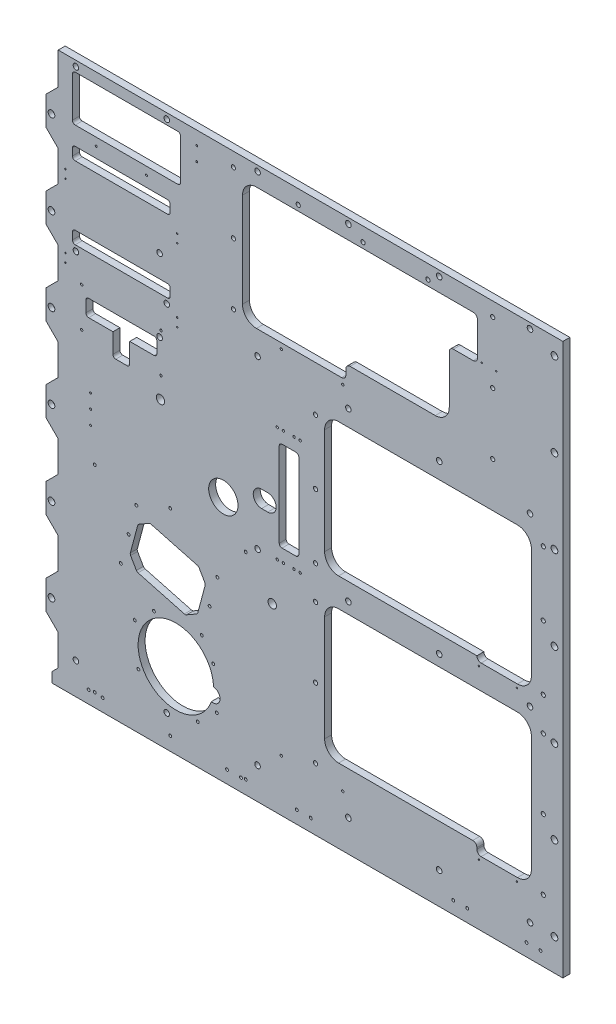
SolidWorks part; units mm, degrees
ref_plane "前视基准面" through (0, 0, 0) normal (0, 0, 1) x (1, 0, 0)
ref_plane "上视基准面" through (0, 0, 0) normal (0, 1, 0) x (1, 0, 0)
ref_plane "右视基准面" through (0, 0, 0) normal (1, 0, 0) x (0, 0, -1)
sketch "草图1" plane through (0, 0, 0) normal (0, 0, 1) x (1, 0, 0)
  line L1 (-930, 986.5) -> (930, 986.5)
  line L2 (-930, 986.5) -> (-930, -986.5)
  line L3 (-930, -986.5) -> (930, -986.5)
  line L4 (930, 986.5) -> (930, -986.5)
  line L5 (-930, 986.5) -> (930, -986.5) construction
  line L6 (-930, -986.5) -> (930, 986.5) construction
  point P0 (0, 0)
  dimension "D1" = 1973
  dimension "D2" = 1860
base flange "基体-法兰1" sketch "草图1" thickness 25 reverse thickness direction no parameters "D1"=1
sketch "草图6" plane through (0, 0, 0) normal (0, 0, 1) x (1, 0, 0)
  line L0 (-876, 871.5) -> (-919, 828.5)
  line L1 (-876, 986.5) -> (-930, 986.5)
  line L2 (-919, 828.5) -> (-919, 724.5)
  line L3 (-919, 724.5) -> (-876, 681.5)
  line L4 (-876, 571.5) -> (-919, 528.5)
  line L5 (-919, 528.5) -> (-919, 424.5)
  line L6 (-919, 424.5) -> (-876, 381.5)
  line L7 (-876, 271.5) -> (-919, 228.5)
  line L8 (-919, 228.5) -> (-919, 124.5)
  line L9 (-919, 124.5) -> (-876, 81.5)
  line L10 (-876, -28.5) -> (-919, -71.5)
  line L11 (-919, -71.5) -> (-919, -175.5)
  line L12 (-919, -175.5) -> (-876, -218.5)
  line L13 (-876, -328.5) -> (-919, -371.5)
  line L14 (-919, -371.5) -> (-919, -475.5)
  line L15 (-919, -475.5) -> (-876, -518.5)
  line L16 (-876, -628.5) -> (-919, -671.5)
  line L17 (-919, -671.5) -> (-919, -775.5)
  line L18 (-919, -775.5) -> (-876, -818.5)
  line L19 (930, 986.5) -> (-930, 986.5) construction
  line L20 (-876, -928.5) -> (-897.5, -950)
  line L21 (-897.5, -950) -> (-897.5, -986.5)
  line L22 (-930, -986.5) -> (930, -986.5) construction
  line L23 (-876, -818.5) -> (-876, -928.5)
  line L24 (-930, 986.5) -> (-930, -986.5)
  line L25 (-876, 871.5) -> (-876, 986.5)
  line L26 (-876, 681.5) -> (-876, 571.5)
  line L27 (-876, 381.5) -> (-876, 271.5)
  line L28 (-876, 81.5) -> (-876, -28.5)
  line L29 (-876, -218.5) -> (-876, -328.5)
  line L30 (-876, -518.5) -> (-876, -628.5)
  line L31 (-930, 986.5) -> (-930, -986.5) construction
  line L32 (-930, -986.5) -> (-897.5, -986.5)
  point P30 (-897.5, -968.25)
  dimension "D1" = 115
  dimension "D3" = 43
  dimension "D4" = 104
  dimension "D5" = 110
  dimension "D6" = 190
  dimension "D7" = 104
  dimension "D8" = 43
  dimension "D9" = 190
  dimension "D10" = 104
  dimension "D11" = 104
  dimension "D12" = 104
  dimension "D13" = 104
  dimension "D14" = 110
  dimension "D15" = 110
  dimension "D16" = 190
  dimension "D17" = 110
  dimension "D18" = 190
  dimension "D19" = 110
  dimension "D20" = 190
  dimension "D21" = 43
  dimension "D22" = 11
  dimension "D23" = 110
  dimension "D24" = 36.5
  dimension "D25" = 190
  dimension "D26" = 43
  dimension "D27" = 21.5
  dimension "D28" = 21.5
extrude "切除-拉伸2" cut sketch "草图6" against normal through all normal cut yes
sketch "草图8" plane through (0, 0, 0) normal (0, 0, 1) x (1, 0, 0)
  line L0 (930, -986.5) -> (930, 986.5) construction
  line L1 (930, 986.5) -> (-876, 986.5) construction
  line L3 (-919, 724.5) -> (-919, 828.5) construction
  circle A0 centre (900, 926.5) radius 12
  circle A1 centre (900, 626.5) radius 12
  circle A2 centre (900, 326.5) radius 12
  circle A3 centre (900, 26.5) radius 12
  circle A4 centre (900, -273.5) radius 12
  circle A5 centre (900, -573.5) radius 12
  circle A6 centre (900, -873.5) radius 12
  circle A7 centre (-900, 776.5) radius 12
  circle A8 centre (-900, 476.5) radius 12
  circle A9 centre (-900, 176.5) radius 12
  circle A10 centre (-900, -123.5) radius 12
  circle A11 centre (-900, -423.5) radius 12
  circle A12 centre (-900, -723.5) radius 12
  point P17 (930, 0)
  dimension "D1" = 30
  dimension "D2" = 24
  dimension "D3" = 24
  dimension "D4" = 24
  dimension "D5" = 24
  dimension "D6" = 24
  dimension "D7" = 24
  dimension "D8" = 24
  dimension "D9" = 60
  dimension "D10" = 300
  dimension "D11" = 300
  dimension "D12" = 300
  dimension "D13" = 300
  dimension "D15" = 300
  dimension "D16" = 210
  dimension "D17" = 300
  dimension "D18" = 300
  dimension "D19" = 300
  dimension "D20" = 300
  dimension "D21" = 300
  dimension "D22" = 24
  dimension "D23" = 24
  dimension "D24" = 24
  dimension "D25" = 24
  dimension "D26" = 24
  dimension "D27" = 24
  dimension "D28" = 19
  dimension "D14" = 300
extrude "切除-拉伸3" cut sketch "草图8" against normal blind 16 normal cut yes
sketch "草图10" plane through (0, 0, 0) normal (0, 0, 1) x (1, 0, 0)
  line L1 (930, 986.5) -> (-876, 986.5) construction
  line L2 (-919, 724.5) -> (-919, 828.5) construction
  line L3 (-919, 424.5) -> (-919, 528.5) construction
  line L4 (-919, -775.5) -> (-919, -671.5) construction
  circle A0 centre (-812.5, 966.5) radius 10
  circle A1 centre (-487.5, 966.5) radius 10
  circle A2 centre (-162.5, 966.5) radius 10
  circle A3 centre (162.5, 966.5) radius 10
  circle A4 centre (487.5, 966.5) radius 10
  circle A5 centre (812.5, 966.5) radius 10
  circle A6 centre (-812.5, 394.5) radius 10
  circle A7 centre (487.5, 394.5) radius 10
  circle A8 centre (812.5, 394.5) radius 10
  circle A9 centre (162.5, 394.5) radius 10
  circle A10 centre (-162.5, 394.5) radius 10
  circle A11 centre (-487.5, 394.5) radius 10
  circle A12 centre (812.5, -203.5) radius 10
  circle A14 centre (487.5, -203.5) radius 10
  circle A15 centre (-162.5, -203.5) radius 10
  circle A16 centre (162.5, -203.5) radius 10
  circle A18 centre (812.5, -873.5) radius 10
  circle A19 centre (-487.5, -873.5) radius 10
  circle A20 centre (-812.5, -873.5) radius 10
  circle A21 centre (-162.5, -873.5) radius 10
  circle A22 centre (162.5, -873.5) radius 10
  circle A23 centre (487.5, -873.5) radius 10
  dimension "D1" = 325
  dimension "D2" = 325
  dimension "D3" = 325
  dimension "D4" = 325
  dimension "D5" = 325
  dimension "D6" = 106.5
  dimension "D7" = 20
  dimension "D8" = 20
  dimension "D9" = 20
  dimension "D10" = 20
  dimension "D11" = 20
  dimension "D12" = 20
  dimension "D13" = 20
  dimension "D14" = 20
  dimension "D15" = 20
  dimension "D16" = 20
  dimension "D17" = 20
  dimension "D18" = 20
  dimension "D19" = 20
  dimension "D20" = 20
  dimension "D21" = 20
  dimension "D22" = 20
  dimension "D23" = 20
  dimension "D24" = 20
  dimension "D25" = 20
  dimension "D26" = 325
  dimension "D27" = 325
  dimension "D28" = 20
  dimension "D29" = 20
  dimension "D30" = 20
  dimension "D31" = 20
  dimension "D32" = 572
  dimension "D34" = 670
  dimension "D35" = 325
  dimension "D36" = 106.5
  dimension "D38" = 325
  dimension "D39" = 325
  dimension "D41" = 325
  dimension "D42" = 325
  dimension "D43" = 325
  dimension "D44" = 325
  dimension "D45" = 325
  dimension "D46" = 325
  dimension "D47" = 325
  dimension "D48" = 106.5
  dimension "D33" = 598
  dimension "D37" = 325
  dimension "D40" = 325
extrude "切除-拉伸5" cut sketch "草图10" against normal blind 16 normal cut yes
sketch "草图9" plane through (0, 0, 0) normal (0, 0, 1) x (1, 0, 0)
  circle A0 centre (900, 926.5) radius 7
  circle A1 centre (900, 626.5) radius 7
  circle A2 centre (900, 326.5) radius 7
  circle A3 centre (900, 26.5) radius 7
  circle A4 centre (900, -273.5) radius 7
  circle A5 centre (900, -573.5) radius 7
  circle A6 centre (900, -873.5) radius 7
  circle A7 centre (-900, 776.5) radius 7
  circle A8 centre (-900, 476.5) radius 7
  circle A9 centre (-900, 176.5) radius 7
  circle A10 centre (-900, -123.5) radius 7
  circle A11 centre (-900, -423.5) radius 7
  circle A12 centre (-900, -723.5) radius 7
  circle A14 centre (812.5, 966.5) radius 5.25
  circle A15 centre (487.5, 966.5) radius 5.25
  circle A16 centre (162.5, 966.5) radius 5.25
  circle A17 centre (-162.5, 966.5) radius 5.25
  circle A18 centre (-487.5, 966.5) radius 5.25
  circle A19 centre (-812.5, 966.5) radius 5.25
  circle A20 centre (-812.5, 394.5) radius 5.25
  circle A21 centre (-487.5, 394.5) radius 5.25
  circle A22 centre (-162.5, 394.5) radius 5.25
  circle A23 centre (162.5, 394.5) radius 5.25
  circle A24 centre (487.5, 394.5) radius 5.25
  circle A25 centre (812.5, 394.5) radius 5.25
  circle A26 centre (812.5, -203.5) radius 5.25
  circle A27 centre (487.5, -203.5) radius 5.25
  circle A28 centre (162.5, -203.5) radius 5.25
  circle A29 centre (-162.5, -203.5) radius 5.25
  circle A30 centre (-812.5, -873.5) radius 5.25
  circle A31 centre (-487.5, -873.5) radius 5.25
  circle A32 centre (-162.5, -873.5) radius 5.25
  circle A33 centre (162.5, -873.5) radius 5.25
  circle A34 centre (487.5, -873.5) radius 5.25
  circle A35 centre (812.5, -873.5) radius 5.25
  dimension "D1" = 14
  dimension "D2" = 14
  dimension "D3" = 14
  dimension "D4" = 14
  dimension "D5" = 14
  dimension "D6" = 14
  dimension "D7" = 14
  dimension "D9" = 14
  dimension "D10" = 14
  dimension "D11" = 14
  dimension "D12" = 14
  dimension "D13" = 14
  dimension "D14" = 14
  dimension "D15" = 10.5
  dimension "D16" = 10.5
  dimension "D17" = 10.5
  dimension "D18" = 10.5
  dimension "D19" = 10.5
  dimension "D20" = 10.5
  dimension "D21" = 10.5
  dimension "D22" = 10.5
  dimension "D23" = 10.5
  dimension "D24" = 10.5
  dimension "D25" = 10.5
  dimension "D26" = 10.5
  dimension "D27" = 10.5
  dimension "D28" = 10.5
  dimension "D29" = 10.5
  dimension "D30" = 10.5
  dimension "D31" = 10.5
  dimension "D32" = 10.5
  dimension "D33" = 10.5
  dimension "D34" = 10.5
  dimension "D35" = 10.5
  dimension "D36" = 10.5
extrude "切除-拉伸4" cut sketch "草图9" against normal through all normal cut yes
sketch "草图11" plane through (0, 0, 0) normal (0, 0, 1) x (1, 0, 0)
  line L0 (-650, -280.615) -> (-650, 1050.9989) construction
  line L2 (-523, 271.5) -> (-777, 271.5)
  line L3 (-825, 948.5) -> (-438, 948.5)
  line L4 (-825, 948.5) -> (-825, 784.5)
  line L5 (-825, 784.5) -> (-438, 784.5)
  line L6 (-438, 948.5) -> (-438, 784.5)
  line L7 (-825, 718.5) -> (-475, 718.5)
  line L8 (-825, 718.5) -> (-825, 673.5)
  line L9 (-825, 673.5) -> (-475, 673.5)
  line L10 (-475, 718.5) -> (-475, 673.5)
  line L11 (-825, 458.5) -> (-475, 458.5)
  line L12 (-825, 458.5) -> (-825, 413.5)
  line L13 (-825, 413.5) -> (-475, 413.5)
  line L14 (-475, 458.5) -> (-475, 413.5)
  line L15 (-777, 271.5) -> (-777, 211.5)
  line L16 (-777, 211.5) -> (-680, 211.5)
  line L17 (-680, 211.5) -> (-680, 131.5)
  line L18 (-680, 131.5) -> (-620, 131.5)
  line L19 (-620, 211.5) -> (-620, 131.5)
  line L20 (-523, 211.5) -> (-620, 211.5)
  line L21 (-523, 271.5) -> (-523, 211.5)
  line L22 (930, 986.5) -> (-876, 986.5) construction
  line L23 (-216.5, 916.5) -> (624.5, 916.5)
  line L24 (624.5, 916.5) -> (624.5, 766.5)
  line L25 (624.5, 766.5) -> (523.5, 766.5)
  line L26 (523.5, 766.5) -> (523.5, 528.5)
  line L27 (523.5, 528.5) -> (153.5, 528.5)
  line L28 (-216.5, 478.5) -> (-216.5, 916.5)
  line L29 (153.5, 528.5) -> (153.5, 478.5)
  line L30 (153.5, 478.5) -> (-216.5, 478.5)
  line L31 (77.5, -141.5) -> (622.5, -141.5)
  line L32 (77.5, 336.5) -> (817.5, 336.5)
  line L33 (77.5, 336.5) -> (77.5, -141.5)
  line L34 (622.5, -141.5) -> (622.5, -156.5)
  line L35 (817.5, 336.5) -> (817.5, -156.5)
  line L36 (77.5, -243.5) -> (817.5, -243.5)
  line L37 (77.5, -243.5) -> (77.5, -721.5)
  line L38 (622.5, -156.5) -> (817.5, -156.5)
  line L39 (817.5, -243.5) -> (817.5, -756.5)
  line L40 (77.5, -721.5) -> (622.5, -721.5)
  line L41 (622.5, -721.5) -> (622.5, -756.5)
  line L42 (622.5, -756.5) -> (817.5, -756.5)
  line L43 (930, -986.5) -> (-897.5, -986.5) construction
  line L45 (-455, -763.5) -> (-455, -280.615) construction
  line L46 (-85, 165.5) -> (-15, 165.5)
  line L47 (-85, 165.5) -> (-85, -156.5)
  line L48 (-85, -156.5) -> (-15, -156.5)
  line L49 (-15, 165.5) -> (-15, -156.5)
  line L50 (-148, -40.5) -> (-126, -40.5) construction
  line L51 (-148, -10.5) -> (-126, -10.5)
  line L52 (-148, -70.5) -> (-126, -70.5)
  line L53 (-634.6101, -713.5) -> (-251.5936, -713.5) construction
  line L54 (-286.4274, -758.6689) -> (-643.002, -663.125) construction
  line L55 (-584.6566, -399.2341) -> (-148.2438, -516.1705) construction
  line L56 (-501.364, -886.5328) -> (-393.6555, -484.559) construction
  line L57 (-771.324, -663.3992) -> (-210.7397, -752.187) construction
  line L58 (-462.511, -346.2746) -> (-501.0754, -490.1988) construction
  line L59 (-339.8986, -371.6419) -> (-581.3801, -306.9371)
  line L60 (-581.3801, -306.9371) -> (-627.9675, -480.8038)
  line L61 (-627.9675, -480.8038) -> (-386.4861, -545.5085)
  line L62 (-339.8986, -371.6419) -> (-386.4861, -545.5085)
  line L63 (0, 0) -> (0, -1303.0054) construction
  line L64 (-919, 724.5) -> (-919, 828.5) construction
  line L65 (930, -986.5) -> (930, 986.5) construction
  circle A0 centre (-249, 936.5) radius 7.5
  circle A1 centre (-249, 716.5) radius 7.5
  circle A2 centre (-249, 496.5) radius 7.5
  circle A3 centre (-17, 936.5) radius 7.5
  circle A4 centre (215, 936.5) radius 7.5
  circle A5 centre (447, 936.5) radius 7.5
  circle A6 centre (679, 936.5) radius 7.5
  circle A7 centre (679, 716.5) radius 7.5
  circle A8 centre (679, 496.5) radius 7.5
  circle A9 centre (-380, 938.5) radius 3.4
  circle A10 centre (-380, 888.5) radius 3.4
  circle A11 centre (-740, 756.5) radius 3.4
  circle A12 centre (-560, 756.5) radius 3.4
  circle A13 centre (-513, 538.5) radius 10
  circle A14 centre (-513, 278.5) radius 10
  circle A15 centre (-850, 630.5) radius 2.55
  circle A16 centre (-850, 600.5) radius 2.55
  circle A17 centre (-850, 370.5) radius 2.55
  circle A18 centre (-850, 340.5) radius 2.55
  circle A19 centre (-450, 340.5) radius 2.55
  circle A20 centre (-450, 370.5) radius 2.55
  circle A21 centre (-450, 600.5) radius 2.55
  circle A22 centre (-450, 630.5) radius 2.55
  circle A23 centre (-792, 301.5) radius 4.25
  circle A24 centre (-792, 161.5) radius 4.25
  circle A25 centre (-508, 161.5) radius 4.25
  circle A26 centre (-508, 301.5) radius 4.25
  circle A27 centre (-510, 86.5) radius 15
  circle A28 centre (-760, -18.5) radius 3.4
  circle A29 centre (-760, -68.5) radius 3.4
  circle A30 centre (-760, -118.5) radius 3.4
  circle A31 centre (639.5, 775) radius 2.55
  circle A32 centre (691.5, 775) radius 2.55
  circle A33 centre (45, 316.5) radius 7.5
  circle A34 centre (860, 316.5) radius 7.5
  circle A35 centre (860, 86.5) radius 7.5
  circle A36 centre (860, -263.5) radius 7.5
  circle A37 centre (45, 86.5) radius 7.5
  circle A38 centre (45, -263.5) radius 7.5
  circle A39 centre (45, -143.5) radius 7.5
  circle A40 centre (45, -763.5) radius 7.5
  circle A41 centre (45, -513.5) radius 7.5
  circle A42 centre (860, -143.5) radius 7.5
  circle A43 centre (860, -763.5) radius 7.5
  circle A44 centre (860, -513.5) radius 7.5
  circle A45 centre (-77.5, 458.5) radius 4.25
  circle A46 centre (142.5, 458.5) radius 4.25
  circle A47 centre (629.5, -170) radius 2.55
  circle A48 centre (765.5, -170) radius 2.55
  circle A49 centre (629.5, -770) radius 2.55
  circle A50 centre (765.5, -770) radius 2.55
  circle A51 centre (-717, -941.5) radius 5.15
  circle A52 centre (-767, -941.5) radius 5.15
  circle A53 centre (-272, -941.5) radius 5.15
  circle A54 centre (-222, -941.5) radius 5.15
  circle A55 centre (-22, -941.5) radius 5.15
  circle A56 centre (28, -941.5) radius 5.15
  circle A57 centre (800, -941.5) radius 5.15
  circle A58 centre (538, -941.5) radius 5.15
  circle A59 centre (588, -941.5) radius 5.15
  circle A60 centre (850, -941.5) radius 5.15
  circle A61 centre (142.5, -801.5) radius 4.25
  circle A62 centre (-77.5, -801.5) radius 4.25
  circle A63 centre (-92, 209.5) radius 4.25
  circle A64 centre (-70, 209.5) radius 4.25
  circle A65 centre (-32, 209.5) radius 4.25
  circle A66 centre (-10, 209.5) radius 4.25
  circle A67 centre (-92, -200.5) radius 4.25
  circle A68 centre (-70, -200.5) radius 4.25
  circle A69 centre (-10, -200.5) radius 4.25
  circle A70 centre (-32, -200.5) radius 4.25
  arc A71 (-148, -10.5) -> (-148, -70.5) centre (-148, -40.5) ccw
  arc A72 (-126, -70.5) -> (-126, -10.5) centre (-126, -40.5) ccw
  circle A73 centre (-110, -346.5) radius 15
  arc A74 (-320.0543, -709.6704) -> (-327.8425, -758.8427) centre (-455, -713.5) ccw
  circle A75 centre (-745, -938.5) radius 5.15
  circle A76 centre (-475, -938.5) radius 5.15
  circle A77 centre (-205, -938.5) radius 5.15
  circle A78 centre (-745, -233.5) radius 5.15
  circle A79 centre (-475, -233.5) radius 5.15
  circle A80 centre (-205, -233.5) radius 5.15
  circle A81 centre (-285, -103.5) radius 52.5
  circle A82 centre (-533.4288, -581.1929) radius 5.15
  circle A83 centre (-601.7836, -643.1112) radius 5.15
  circle A84 centre (-589.0749, -788.8669) radius 5.15
  circle A85 centre (-376.5712, -845.8071) radius 5.15
  circle A86 centre (-292.6873, -725.9333) radius 5.15 construction
  circle A87 centre (-320.9251, -638.1331) radius 5.15
  arc A88 (-327.8425, -758.8427) -> (-320.0543, -709.6704) centre (-321.6621, -734.6187) ccw
  circle A89 centre (-596.1693, -284.8571) radius 5.15
  circle A90 centre (-306.3915, -362.5028) radius 5.15
  circle A91 centre (-362.0376, -570.1768) radius 5.15
  circle A92 centre (-651.8154, -492.5311) radius 5.15
  circle A93 centre (-334.2146, -466.3398) radius 5.15
  circle A94 centre (-623.9923, -388.6941) radius 5.15
  circle A95 centre (-308.2164, -783.8888) radius 5.15
  circle A96 centre (-617.3127, -701.0667) radius 5.15 construction
  point P23 (-650, 131.5)
  point P26 (-650, 271.5)
  point P202 (-137, -40.5)
  point P256 (-507.2268, -513.1562)
  point P257 (-460.6394, -339.2895)
  dimension "D19" = 401
  dimension "D20" = 928
  dimension "D21" = 220
  dimension "D22" = 220
  dimension "D23" = 232
  dimension "D24" = 232
  dimension "D25" = 232
  dimension "D26" = 15
  dimension "D27" = 15
  dimension "D28" = 15
  dimension "D29" = 15
  dimension "D30" = 15
  dimension "D31" = 15
  dimension "D32" = 15
  dimension "D33" = 15
  dimension "D34" = 15
  dimension "D44" = 6.8
  dimension "D45" = 6.8
  dimension "D46" = 48
  dimension "D47" = 50
  dimension "D48" = 131
  dimension "D49" = 180
  dimension "D50" = 6.8
  dimension "D52" = 135
  dimension "D53" = 260
  dimension "D54" = 20
  dimension "D55" = 20
  dimension "D56" = 137
  dimension "D57" = 126
  dimension "D58" = 30
  dimension "D59" = 230
  dimension "D60" = 30
  dimension "D61" = 5.1
  dimension "D62" = 5.1
  dimension "D63" = 5.1
  dimension "D64" = 5.1
  dimension "D65" = 400
  dimension "D66" = 39
  dimension "D67" = 140
  dimension "D68" = 284
  dimension "D69" = 8.5
  dimension "D70" = 8.5
  dimension "D71" = 45
  dimension "D72" = 140
  dimension "D73" = 30
  dimension "D74" = 180
  dimension "D75" = 50
  dimension "D76" = 50
  dimension "D77" = 110
  dimension "D78" = 6.8
  dimension "D79" = 6.8
  dimension "D80" = 6.8
  dimension "D81" = 52
  dimension "D82" = 15
  dimension "D84" = 5.1
  dimension "D85" = 5.1
  dimension "D91" = 294
  dimension "D92" = 32.5
  dimension "D93" = 15
  dimension "D94" = 815
  dimension "D95" = 620
  dimension "D96" = 15
  dimension "D97" = 15
  dimension "D98" = 15
  dimension "D99" = 15
  dimension "D100" = 15
  dimension "D101" = 15
  dimension "D102" = 15
  dimension "D103" = 15
  dimension "D104" = 15
  dimension "D105" = 15
  dimension "D106" = 15
  dimension "D108" = 230
  dimension "D109" = 230
  dimension "D110" = 120
  dimension "D111" = 250
  dimension "D112" = 250
  dimension "D113" = 20
  dimension "D115" = 220
  dimension "D116" = 8.5
  dimension "D117" = 8.5
  dimension "D122" = 28.5
  dimension "D123" = 5.1
  dimension "D124" = 5.1
  dimension "D125" = 136
  dimension "D127" = 5.1
  dimension "D128" = 5.1
  dimension "D130" = 50
  dimension "D131" = 10.3
  dimension "D132" = 10.3
  dimension "D133" = 45
  dimension "D134" = 80
  dimension "D135" = 50
  dimension "D136" = 50
  dimension "D137" = 50
  dimension "D138" = 50
  dimension "D139" = 445
  dimension "D140" = 200
  dimension "D141" = 510
  dimension "D142" = 212
  dimension "D143" = 45
  dimension "D144" = 10.3
  dimension "D145" = 10.3
  dimension "D146" = 10.3
  dimension "D147" = 10.3
  dimension "D148" = 10.3
  dimension "D149" = 10.3
  dimension "D150" = 10.3
  dimension "D151" = 10.3
  dimension "D152" = 45
  dimension "D153" = 45
  dimension "D154" = 45
  dimension "D155" = 38
  dimension "D156" = 8.5
  dimension "D157" = 8.5
  dimension "D159" = 220
  dimension "D160" = 22
  dimension "D161" = 22
  dimension "D162" = 38
  dimension "D163" = 195
  dimension "D166" = 7
  dimension "D167" = 777
  dimension "D168" = 44
  dimension "D169" = 8.5
  dimension "D170" = 8.5
  dimension "D171" = 8.5
  dimension "D172" = 8.5
  dimension "D173" = 8.5
  dimension "D174" = 8.5
  dimension "D175" = 8.5
  dimension "D176" = 8.5
  dimension "D177" = 410
  dimension "D179" = 250
  dimension "D181" = 30
  dimension "D183" = 30
  dimension "D184" = 146
  dimension "D185" = 100
  dimension "D186" = 270
  dimension "D188" = 270
  dimension "D189" = 270
  dimension "D191" = 225
  dimension "D192" = 10.3
  dimension "D193" = 10.3
  dimension "D194" = 10.3
  dimension "D195" = 10.3
  dimension "D196" = 10.3
  dimension "D197" = 10.3
  dimension "D198" = 705
  dimension "D201" = 105
  dimension "D202" = 130
  dimension "D203" = 190
  dimension "D204" = 220
  dimension "D205" = 30
  dimension "D206" = 320
  dimension "D207" = 107.5
  dimension "D208" = 107.5
  dimension "D209" = 220
  dimension "D210" = 10.3
  dimension "D211" = 10.3
  dimension "D212" = 10.3
  dimension "D214" = 25
  dimension "D219" = 145
  dimension "D220" = 145
  dimension "D221" = 155
  dimension "D222" = 155
  dimension "D223" = 215
  dimension "D224" = 215
  dimension "D225" = 10.3
  dimension "D226" = 10.3
  dimension "D227" = 10.3
  dimension "D228" = 10.3
  dimension "D229" = 30
  dimension "D230" = 10.3
  dimension "D231" = 320
  dimension "D2" = 175
  dimension "D3" = 212
  dimension "D4" = 38
  dimension "D5" = 164
  dimension "D6" = 175
  dimension "D7" = 175
  dimension "D8" = 66
  dimension "D9" = 45
  dimension "D10" = 215
  dimension "D11" = 45
  dimension "D12" = 175
  dimension "D13" = 175
  dimension "D14" = 142
  dimension "D15" = 60
  dimension "D16" = 80
  dimension "D17" = 60
  dimension "D18" = 254
  dimension "D35" = 50
  dimension "D36" = 841
  dimension "D37" = 238
  dimension "D38" = 50
  dimension "D39" = 32.5
  dimension "D40" = 101
  dimension "D41" = 370
  dimension "D42" = 438
  dimension "D43" = 70
  dimension "D51" = 230
  dimension "D83" = 141.5
  dimension "D86" = 740
  dimension "D87" = 740
  dimension "D88" = 478
  dimension "D89" = 102
  dimension "D90" = 142
  dimension "D107" = 478
  dimension "D114" = 65
  dimension "D118" = 35
  dimension "D119" = 195
  dimension "D120" = 195
  dimension "D121" = 15
  dimension "D126" = 52
  dimension "D129" = 48.5
  dimension "D158" = 65
  dimension "D164" = 445
  dimension "D165" = 70
  dimension "D178" = 322
  dimension "D180" = 45
  dimension "D182" = 22
  dimension "D187" = 1700
  dimension "D190" = 20
  dimension "D199" = 15
  dimension "D200" = 270
  dimension "D213" = 6
  dimension "D215" = 102.3
  dimension "D216" = 250
  dimension "D217" = 90
  dimension "D218" = 90
  dimension "D232" = 269
extrude "切除-拉伸6" cut sketch "草图11" against normal through all normal cut yes
fillet "圆角1" radius 10 18 edges at (-523, 271.5, -12.5) (-523, 211.5, -12.5) (-620, 131.5, -12.5) (-777, 271.5, -12.5) (-777, 211.5, -12.5) (-680, 131.5, -12.5) (-475, 413.5, -12.5) (-825, 413.5, -12.5) (-825, 458.5, -12.5) (-475, 458.5, -12.5) (-825, 673.5, -12.5) (-825, 718.5, -12.5) (-475, 673.5, -12.5) (-475, 718.5, -12.5) (-825, 784.5, -12.5) (-438, 784.5, -12.5) (-438, 948.5, -12.5) (-825, 948.5, -12.5)
fillet "圆角2" radius 50 3 edges at (523.5, 528.5, -12.5) (-216.5, 478.5, -12.5) (-216.5, 916.5, -12.5)
fillet "圆角3" radius 15 5 edges at (624.5, 916.5, -12.5) (624.5, 766.5, -12.5) (523.5, 766.5, -12.5) (153.5, 528.5, -12.5) (153.5, 478.5, -12.5)
fillet "圆角4" radius 50 8 edges at (817.5, -756.5, -12.5) (817.5, -243.5, -12.5) (77.5, -721.5, -12.5) (77.5, -243.5, -12.5) (77.5, -141.5, -12.5) (817.5, -156.5, -12.5) (817.5, 336.5, -12.5) (77.5, 336.5, -12.5)
fillet "圆角5" radius 15 3 edges at (622.5, -156.5, -12.5) (622.5, -756.5, -12.5) (622.5, -721.5, -12.5)
fillet "圆角6" radius 10 4 edges at (-85, -156.5, -12.5) (-15, -156.5, -12.5) (-15, 165.5, -12.5) (-85, 165.5, -12.5)
chamfer "倒角1" distance 35 angle 45 4 edges at (-581.3801, -306.9371, -12.5) (-627.9675, -480.8038, -12.5) (-386.4861, -545.5085, -12.5) (-339.8986, -371.6419, -12.5)
fillet "圆角7" radius 10 8 edges at (-547.5727, -315.9958, -12.5) (-590.4388, -340.7445, -12.5) (-618.9088, -446.9964, -12.5) (-594.1601, -489.8624, -12.5) (-420.2935, -536.4499, -12.5) (-377.4274, -511.7011, -12.5) (-348.9573, -405.4493, -12.5) (-373.706, -362.5832, -12.5)
sketch "折弯-线1" plane through (0, 0, 0) normal (0, 1, 0) x (1, 0, 0)
sketch "边界框1" plane through (0, 0, 0) normal (0, 1, 0) x (1, 0, 0)
sheet metal parameters "钣金6" thickness 25 parameters "D1"=1
flat pattern "平板型式6" [suppressed]
sketch "折弯-线2" plane through (0, 0, 0) normal (0, 1, 0) x (1, 0, 0)
sketch "边界框2" [suppressed] plane through (0, 0, 0) normal (0, 1, 0) x (1, 0, 0)
sheet metal parameters "钣金7" thickness 25 parameters "D1"=1
flat pattern "平板型式6"
sketch "折弯-线2" plane through (0, 0, 0) normal (0, 1, 0) x (1, 0, 0)
sketch "边界框2" [suppressed] plane through (0, 0, 0) normal (0, 1, 0) x (1, 0, 0)
sheet metal parameters "钣金8" thickness 25 parameters "D1"=1
flat pattern "平板型式6"
sketch "折弯-线2" plane through (0, 0, 0) normal (0, 1, 0) x (1, 0, 0)
sketch "边界框2" [suppressed] plane through (0, 0, 0) normal (0, 1, 0) x (1, 0, 0)
sheet metal parameters "钣金9" thickness 25 parameters "D1"=1
flat pattern "平板型式6"
sketch "折弯-线2" plane through (0, 0, 0) normal (0, 1, 0) x (1, 0, 0)
sketch "边界框2" [suppressed] plane through (0, 0, 0) normal (0, 1, 0) x (1, 0, 0)
sheet metal parameters "钣金10" thickness 25 parameters "D1"=1
flat pattern "平板型式6"
sketch "折弯-线2" plane through (0, 0, 0) normal (0, 1, 0) x (1, 0, 0)
sketch "边界框2" [suppressed] plane through (0, 0, 0) normal (0, 1, 0) x (1, 0, 0)
sheet metal parameters "钣金11" thickness 25 parameters "D1"=1
flat pattern "平板型式6"
sketch "折弯-线2" plane through (0, 0, 0) normal (0, 1, 0) x (1, 0, 0)
sketch "边界框2" [suppressed] plane through (0, 0, 0) normal (0, 1, 0) x (1, 0, 0)
